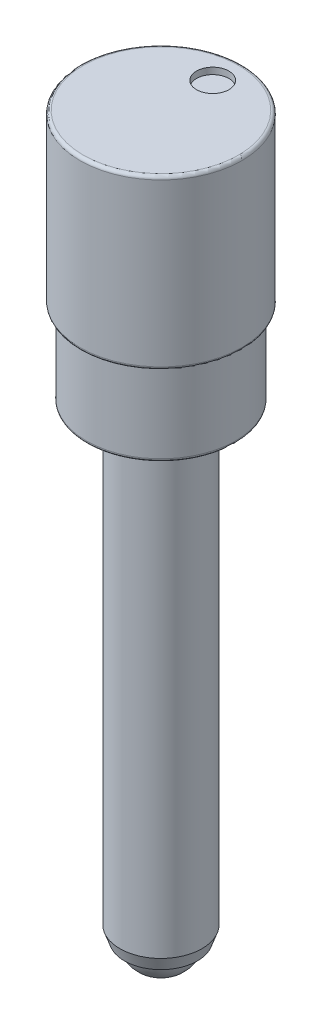
SolidWorks part; units mm, degrees
note: '?' marks a value the reader was unsure of.
ref_plane "Front Plane" through (0, 0, 0) normal (0, 0, 1) x (1, 0, 0)
ref_plane "Top Plane" through (0, 0, 0) normal (0, 1, 0) x (1, 0, 0)
ref_plane "Right Plane" through (0, 0, 0) normal (1, 0, 0) x (0, 0, -1)
sketch "Sketch1" plane through (0, 0, 0) normal (0, 1, 0) x (1, 0, 0)
  circle A0 centre (0, 0) radius 6.25
  dimension "D1" = 12.5
extrude "top head with knurling" add sketch "Sketch1" along normal blind 13
sketch "Sketch2" plane through (0, 0, 0) normal (0, -1, 0) x (1, 0, 0)
  circle A0 centre (0, 0) radius 5.75
  dimension "D1" = 11.5
extrude "flat bottom of head" add sketch "Sketch2" along normal blind 6.5
fillet "Fillet1" radius 0.25 3 edges at (0, -6.5, -5.75) (0, 0, 6.25) (0, 13, 6.25)
sketch "Sketch3" plane through (0, -6.5, 0) normal (0, -1, 0) x (1, 0, 0)
  circle A0 centre (0, 0) radius 3.175
  dimension "D1" = 6.35
extrude "screw piece" add sketch "Sketch3" along normal blind 35 separate body
sketch "Sketch4" plane through (0, -41.5, 0) normal (0, -1, 0) x (-1, 0, 0)
  circle A0 centre (0, 0) radius 3.175
  circle A1 centre (0, 0) radius 3.175 construction
extrude "drafted screw end" add sketch "Sketch4" along normal blind 1 draft 19.5
sketch "Sketch6" plane through (0, -42.5, 0) normal (0, -1, 0) x (1, 0, 0)
  circle A0 centre (0, 0) radius 2.5
  dimension "D1" = 5
extrude "Cut-Extrude1" cut sketch "Sketch6" against normal blind 0.5
sketch "Sketch7" plane through (0, -42, 0) normal (0, -1, 0) x (-1, 0, 0)
  line L0 (2.5, 0) -> (-2.5, 0)
  circle A0 centre (0, 0) radius 2.5 construction
  circle A1 centre (0, 0) radius 2.5 construction
  arc A2 (2.5, 0) -> (-2.5, 0) centre (0, 0) cw
ref_axis "Axis2" through (-2.5, -42, 0) along (1, 0, 0)?
revolve "Revolve3" add sketch "Sketch7" angle 180 about L0
sketch "Sketch8" plane through (0, 13, 0) normal (0, 1, 0) x (1, 0, 0)
  line L0 (0, 0) -> (0, 4) construction
  circle A0 centre (0, 4) radius 1.25
  dimension "D2" = 2.5
  dimension "D1" = 4
extrude "Cut-Extrude2" cut sketch "Sketch8" against normal blind 0.5
sketch "Sketch10" plane through (0, -42, 0) normal (0, -1, 0) x (1, 0, 0)
  circle A0 centre (0, 0) radius 0.0766
extrude "Boss-Extrude1" add sketch "Sketch10" along normal offset from surface (2.5088 mm away) 0.01
ref_axis "Axis3" through (0, -41.5, 0) along (0, 1, 0)?
thread "Thread1" [suppressed] pitch 0.3175 start angle 0, offset 0, length 36, pitch 0.3175, diameter 6.35
ref_plane "Plane2" through (-3.175, -42, 0) normal (0, 0, 1) x (-1, 0, 0)
sketch "Thread Profile2" plane through (-3.175, -42, 0) normal (0, 0, 1) x (-1, 0, 0)
  line L0 (0, 0) -> (0, 0.3175) construction
  line L11 (0, 0) -> (0, 0.2778)
  line L12 (0, 0.2778) -> (-0.1719, 0.1786)
  line L13 (-0.1719, 0.1786) -> (-0.1719, 0.0992)
  line L15 (-0.1719, 0.0992) -> (0, 0)
  line L17 (-0.1719, 0.1389) -> (0, 0.1389) construction
  point P2 (0, 0)
  dimension "Pitch" = 0.3175
  dimension "Profile_Angle" = 60
  dimension "Profile_Land" = 0.0794
  dimension "Profile_Height" = 0.1719
